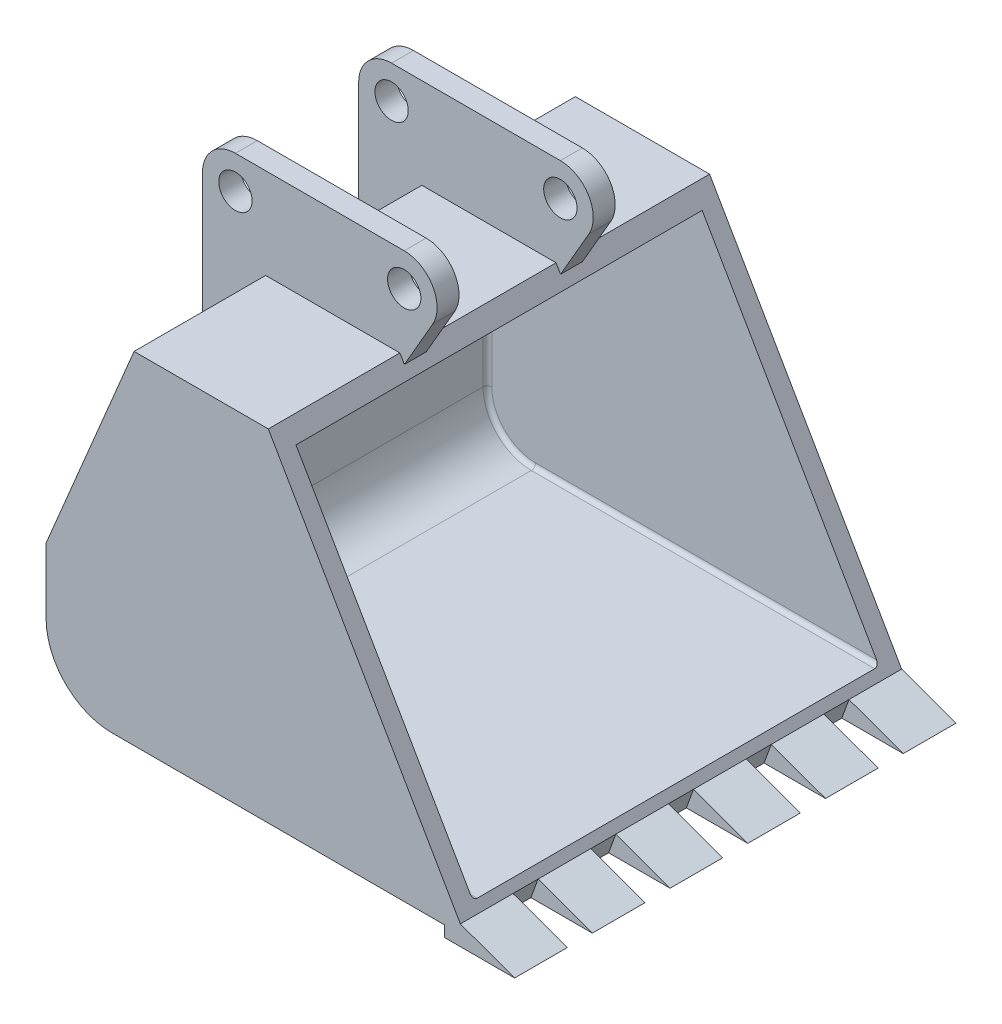
SolidWorks part; units mm, degrees
ref_plane "Front Plane" through (0, 0, 0) normal (0, 0, 1) x (1, 0, 0)
ref_plane "Top Plane" through (0, 0, 0) normal (0, 1, 0) x (1, 0, 0)
ref_plane "Right Plane" through (0, 0, 0) normal (1, 0, 0) x (0, 0, -1)
sketch "Sketch1" plane through (0, 0, 0) normal (0, 0, 1) x (1, 0, 0)
  line L0 (0, 0) -> (758, 0)
  line L1 (-150, 150) -> (-150, 300)
  line L2 (-150, 300) -> (50.523, 778.362)
  line L3 (50.523, 778.362) -> (356.523, 778.362)
  line L5 (758, 0) -> (758, -25)
  line L6 (758, -25) -> (918, -25)
  line L7 (918, -25) -> (794.3635, 20)
  line L8 (794.3635, 20) -> (777.9849, -25)
  line L9 (356.523, 778.362) -> (794.3635, 20)
  arc A0 (0, 0) -> (-150, 150) centre (0, 150) cw
  dimension "D2" = 150
  dimension "D1" = 758
  dimension "D3" = 150
  dimension "D4" = 780
  dimension "D5" = 306
  dimension "D6" = 25
  dimension "D7" = 45
  dimension "D8" = 90
  dimension "D9" = 20
  dimension "D10" = 160
  dimension "D11" = 1068
  dimension "D12" = 60
extrude "Boss-Extrude2" add sketch "Sketch1" along normal mid plane 1006 contours A0 L0 L5 L6 L8 L9 L3 L2 L1 | L7 L8 L6 region at (259.5597, 326.9448, 0) region at (830.1161, -10, 0)
shell "Shell1" thickness 40 removed face at (575.4433, 399.181, 0)
fillet "Fillet1" radius 10 8 edges at (-110, 220.9777, -463) (-77.7817, 72.2183, -463) (-110, 220.9777, 463) (-77.7817, 72.2183, 463) (-16.4361, 515.1587, -463) (391.4083, 40, -463) (-16.4361, 515.1587, 463) (391.4083, 40, 463)
sketch "Sketch8" plane through (99.3508, 272.964, 0) normal (0.342, 0.9397, 0) x (0.9397, -0.342, 0)
  line L0 (739.6171, -503) -> (739.6171, 503) construction
  line L1 (739.6171, 383) -> (871.1883, 383)
  line L2 (739.6171, 383) -> (739.6171, 325.8)
  line L3 (739.6171, 325.8) -> (871.1883, 325.8)
  line L4 (871.1883, 383) -> (871.1883, 325.8)
  line L5 (871.1883, -503) -> (871.1883, 503) construction
  line L6 (871.1883, 503) -> (739.6171, 503) construction
  dimension "D1" = 57.2
  dimension "D2" = 120
extrude "Cut-Extrude5" cut sketch "Sketch8" against normal blind 1006
pattern_linear "LPattern1" count 5 spacing 177.2 along (0, 0, 1) of "Cut-Extrude5"
sketch "Sketch12" plane through (0, 0, 503) normal (0, 0, 1) x (1, 0, 0)
  line L0 (366.7241, 760.6932) -> (431.2758, 872.5)
  line L1 (366.3239, 985) -> (-18.477, 985)
  line L2 (-93.477, 910) -> (-93.477, 434.8397)
  line L3 (-150, 300) -> (50.523, 778.362) construction
  line L4 (356.523, 778.362) -> (794.3635, 20) construction
  line L5 (758, -25) -> (918, -25) construction
  line L6 (0, 0) -> (758, 0) construction
  line L7 (-93.477, 434.8397) -> (50.523, 778.362)
  line L8 (50.523, 778.362) -> (356.523, 778.362)
  line L10 (356.523, 778.362) -> (366.7241, 760.6932)
  arc A0 (431.2758, 872.5) -> (366.3239, 985) centre (366.3239, 910) ccw
  arc A1 (-18.477, 985) -> (-93.477, 910) centre (-18.477, 910) ccw
  circle A2 centre (-18.477, 910) radius 38
  circle A3 centre (366.3239, 910) radius 38
  point P2 (0, 0)
  dimension "D2" = 76
  dimension "D3" = 75
  dimension "D4" = 76
  dimension "D9" = 75
  dimension "D1" = 120
  dimension "D6" = 144
  dimension "D7" = 1010
  dimension "D8" = 910
extrude "Boss-Extrude4" add sketch "Sketch12" along normal blind 50 from offset 350 offset against normal yes
mirror "Mirror2" about plane through (0, 0, 0) normal (0, 0, 1) of "Boss-Extrude4"
sketch "Sketch13" plane through (0, 0, 203) normal (0, 0, 1) x (1, 0, 0)
